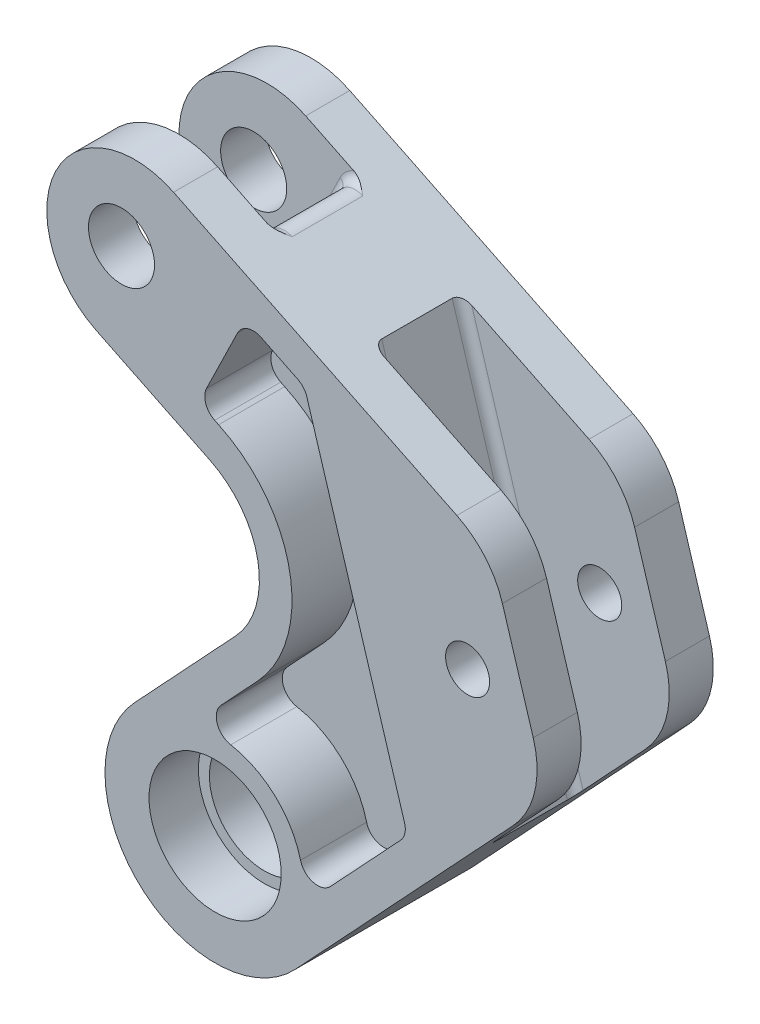
SolidWorks part; units mm, degrees
material "6061-T6 (SS)"
ref_plane "X-Y Datum" through (0, 0, 0) normal (0, 0, 1) x (1, 0, 0)
ref_plane "X-Z Datum" through (0, 0, 0) normal (0, 1, 0) x (1, 0, 0)
ref_plane "Y-Z Datum" through (0, 0, 0) normal (1, 0, 0) x (0, 0, -1)
sketch "Sketch1" plane through (0, 0, 0) normal (0, 0, 1) x (1, 0, 0)
  line L0 (0, 0) -> (36.3909, 38.9981)
  line L1 (31.7483, 64.0948) -> (-19.53, 89.1263)
  line L2 (-30.6723, 66.3007) -> (3.0712, 49.8288)
  line L3 (3.0712, 49.8288) -> (-23.2132, 21.6613)
  line L4 (-11.6066, 10.8306) -> (-25.1012, 77.7135) construction
  line L5 (-25.1012, 77.7135) -> (24.7844, 49.8288) construction
  line L6 (24.7844, 49.8288) -> (-11.6066, 10.8306) construction
  arc A0 (36.3909, 38.9981) -> (31.7483, 64.0948) centre (24.7844, 49.8288) ccw
  arc A1 (-19.53, 89.1263) -> (-30.6723, 66.3007) centre (-25.1012, 77.7135) ccw
  arc A2 (-23.2132, 21.6613) -> (0, 0) centre (-11.6066, 10.8306) ccw
  dimension "D1" = 53.34
  dimension "D2" = 73
  dimension "D3" = 57.15
  dimension "D5" = 25.4
  dimension "D7" = 15.875
  dimension "D8" = 12.7
extrude "Boss-Extrude1" add sketch "Sketch1" along normal blind 25.4 contours L3 A2 L0 A0 L1 A1 L2
fillet "Fillet1" radius 12.7 1 edges at (3.0712, 49.8288, 12.7)
sketch "Sketch2" plane through (0, 0, 25.4) normal (0, 0, 1) x (1, 0, 0)
  circle A0 centre (-11.6066, 10.8306) radius 7.9375
  circle A1 centre (24.7844, 49.8288) radius 3.175
  circle A2 centre (-25.1012, 77.7135) radius 4.7625
  dimension "D1" = 6.35
  dimension "D2" = 9.525
  dimension "D3" = 15.875
extrude "Cut-Extrude1" cut sketch "Sketch2" against normal blind 25.4
sketch "Sketch8" plane through (0, 0, 25.4) normal (0, 0, 1) x (1, 0, 0)
  circle A0 centre (-11.6066, 10.8306) radius 9.525
  dimension "D1" = 19.05
extrude "Cut-Extrude4" cut sketch "Sketch8" against normal blind 7.112
ref_plane "Plane3" through (0, 0, 12.7) normal (0, 0, 1) x (1, 0, 0)
mirror "Mirror1" about plane through (0, 0, 12.7) normal (0, 0, 1) of "Cut-Extrude4"
ref_plane "Plane1" through (-7.789, 25.5073, 0) normal (0.292, -0.9564, 0) x (0, 0, -1)
sketch "Sketch3" plane through (-7.789, 25.5073, 0) normal (0.292, -0.9564, 0) x (0, 0, -1)
  line L0 (-19.05, 54.1313) -> (-19.05, 27.1438)
  line L1 (0, 54.1313) -> (-25.4, 54.1313) construction
  line L2 (-19.05, 27.1438) -> (-6.35, 27.1438)
  line L3 (-6.35, 27.1438) -> (-6.35, 54.1313)
  line L4 (-25.4, 0) -> (-25.4, 46.1938) construction
  line L5 (-25.4, 46.1938) -> (0, 46.1938) construction
  dimension "D1" = 12.7
  dimension "D2" = 6.35
  dimension "D3" = 19.05
extrude "Cut-Extrude2" cut sketch "Sketch3" against normal through all and the other way through all
ref_plane "Plane2" through (31.3765, 64.2763, 0) normal (-0.4387, -0.8986, 0) x (-0.8986, 0.4387, 0)
sketch "Sketch7" plane through (31.3765, 64.2763, 0) normal (-0.4387, -0.8986, 0) x (-0.8986, 0.4387, 0)
  line L6 (-0.4138, 0) -> (56.648, 0) construction
  line L7 (46.488, -19.05) -> (69.983, -19.05)
  line L8 (46.488, -19.05) -> (46.488, -6.35)
  line L9 (46.488, -6.35) -> (69.983, -6.35)
  line L10 (69.983, -19.05) -> (69.983, -6.35)
  line L11 (56.648, -25.4) -> (56.648, 0) construction
  dimension "D1" = 12.7
  dimension "D2" = 6.35
  dimension "D3" = 23.495
  dimension "D4" = 10.16
extrude "Cut-Extrude3" cut sketch "Sketch7" against normal mid plane 53.34
fillet "Fillet2" radius 2.54 2 edges at (-21.5421, 61.8438, 12.7) (-10.3998, 84.6694, 12.7)
fillet "Fillet3" radius 1.27 8 edges at (13.0871, 50.0849, 19.05) (13.0871, 50.0849, 6.35) (-15.9709, 73.2566, 19.05) (-10.0576, 83.6745, 19.05) (-20.5472, 62.1859, 19.05) (-10.0576, 83.6745, 6.35) (-20.5472, 62.1859, 6.35) (-15.9709, 73.2566, 6.35)
sketch3d "3DSketch1"
  line L0 (24.7844, 49.8288, 0) -> (24.7844, 49.8288, 25.4) construction
  line L1 (24.7844, 49.8288, 0) -> (24.7844, 49.8288, 6.35) construction
  line L2 (24.7844, 49.8288, 19.05) -> (24.7844, 49.8288, 25.4) construction
  line L3 (24.7844, 49.8288, 25.4) -> (24.7844, 49.8288, 19.05) construction
  point P8 (24.7844, 49.8288, 12.7)
sketch3d "3DSketch2"
  line L0 (-25.1012, 77.7135, 0) -> (-25.1012, 77.7135, 25.4) construction
  line L1 (-25.1012, 77.7135, 0) -> (-25.1012, 77.7135, 6.35) construction
  line L2 (-25.1012, 77.7135, 19.05) -> (-25.1012, 77.7135, 25.4) construction
  point P6 (-25.1012, 77.7135, 12.7)
sketch "Sketch9" plane through (0, 0, 25.4) normal (0, 0, 1) x (1, 0, 0)
  line L0 (0.8502, 8.3571) -> (16.1244, 24.7256)
  line L1 (16.1244, 24.7256) -> (1.2883, 73.3109)
  line L2 (1.2883, 73.3109) -> (-7.2713, 77.4893)
  line L3 (-7.2713, 77.4893) -> (-13.9567, 63.7939)
  line L4 (-13.9567, 63.7939) -> (-11.1035, 62.4011)
  line L5 (-5.4607, 33.2397) -> (-14.9348, 23.0868)
  line L6 (0, 0) -> (36.3909, 38.9981) construction
  line L7 (28.1982, 65.8278) -> (36.3909, 38.9981)
  line L8 (31.7483, 64.0948) -> (-19.53, 89.1263) construction
  line L9 (-30.6723, 66.3007) -> (-12.3523, 57.3578) construction
  line L10 (-8.6382, 37.2805) -> (-23.2132, 21.6613) construction
  line L11 (36.3909, 38.9981) -> (44.4539, 41.4603)
  line L12 (44.4539, 41.4603) -> (36.2612, 68.2899)
  line L13 (36.2612, 68.2899) -> (28.1982, 65.8278)
  line L15 (-31.4787, 88.6961) -> (-37.6831, 75.986)
  line L16 (-31.4787, 88.6961) -> (-34.5809, 90.2104)
  line L17 (-34.5809, 90.2104) -> (-40.7907, 77.4893)
  line L18 (-40.7907, 77.4893) -> (-37.6831, 75.986)
  arc A0 (0.8502, 8.3571) -> (-14.9348, 23.0868) centre (-11.6066, 10.8306) ccw
  arc A1 (-11.1035, 62.4011) -> (-5.4607, 33.2397) centre (-18.8869, 45.7683) cw
  arc A2 (-19.53, 89.1263) -> (-30.6723, 66.3007) centre (-25.1012, 77.7135) ccw construction
  dimension "D1" = 12.7
  dimension "D9" = 18.3639
  dimension "D2" = 5.08
  dimension "D3" = 120
  dimension "D4" = 5.08
  dimension "D5" = 50.8
  dimension "D6" = 5.08
  dimension "D7" = 9.525
  dimension "D8" = 5.08
  dimension "D10" = 3.175
  dimension "D11" = 26.67
extrude "Cut-Extrude5" cut sketch "Sketch9" against normal blind 9.525
mirror "Mirror2" about plane through (0, 0, 12.7) normal (0, 0, 1) of "Cut-Extrude5"
fillet "Fillet4" radius 2.54 12 edges at (-13.9567, 63.7939, 4.7625) (-14.9348, 23.0868, 4.7625) (0.8502, 8.3571, 4.7625) (16.1244, 24.7256, 4.7625) (1.2883, 73.3109, 4.7625) (-7.2713, 77.4893, 4.7625) (-13.9567, 63.7939, 20.6375) (-7.2713, 77.4893, 20.6375) (1.2883, 73.3109, 20.6375) (16.1244, 24.7256, 20.6375) (0.8502, 8.3571, 20.6375) (-14.9348, 23.0868, 20.6375)
fillet "Fillet5" radius 12.7 8 edges at (36.3909, 38.9981, 3.175) (36.3909, 38.9981, 22.225) (28.1982, 65.8278, 3.175) (28.1982, 65.8278, 22.225) (-37.6831, 75.986, 22.225) (-31.4787, 88.6961, 22.225) (-37.6831, 75.986, 3.175) (-31.4787, 88.6961, 3.175)
